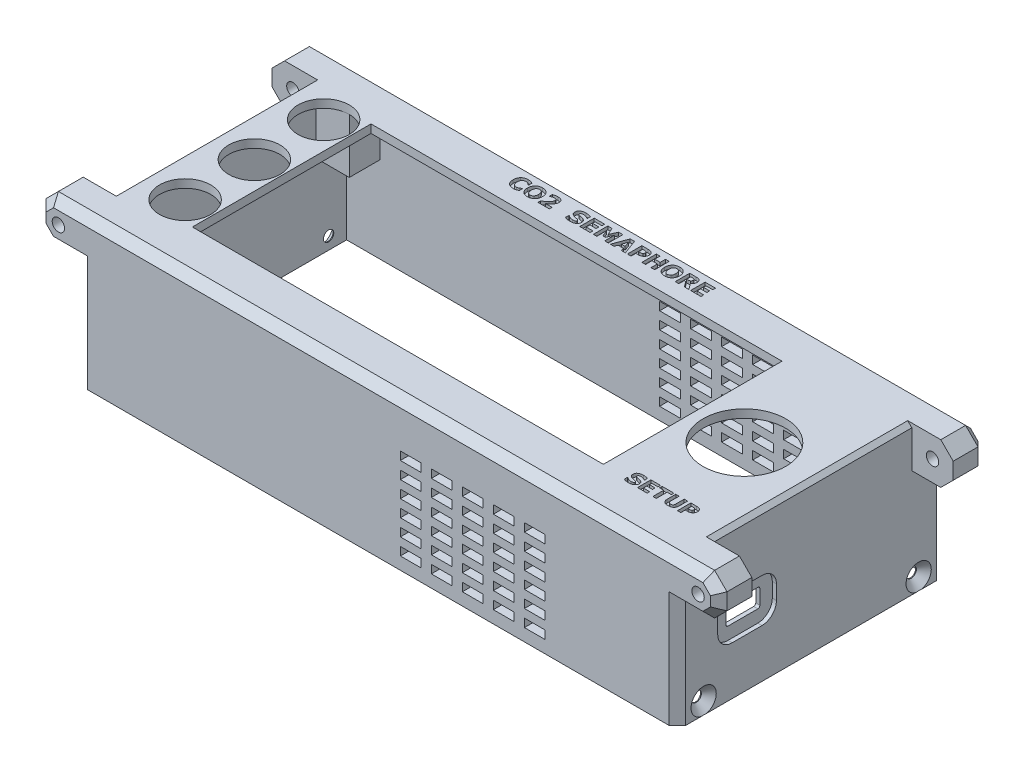
SolidWorks part; units mm, degrees
ref_plane "Спереди" through (0, 0, 0) normal (0, 0, 1) x (1, 0, 0)
ref_plane "Сверху" through (0, 0, 0) normal (0, 1, 0) x (1, 0, 0)
ref_plane "Справа" through (0, 0, 0) normal (1, 0, 0) x (0, 0, -1)
sketch "Эскиз1" plane through (0, 0, 0) normal (0, 1, 0) x (1, 0, 0)
  line L1 (-72.35, 32.35) -> (72.35, 32.35)
  line L2 (-72.35, 32.35) -> (-72.35, -32.35)
  line L3 (-72.35, -32.35) -> (72.35, -32.35)
  line L4 (72.35, 32.35) -> (72.35, -32.35)
  line L5 (-72.35, 32.35) -> (72.35, -32.35) construction
  line L6 (-72.35, -32.35) -> (72.35, 32.35) construction
  point P0 (0, 0)
  dimension "D1" = 144.7
  dimension "D2" = 64.7
extrude "Бобышка-Вытянуть1" add sketch "Эскиз1" along normal blind 36
sketch "Эскиз2" plane through (0, 0, 0) normal (0, -1, 0) x (1, 0, 0)
  line L1 (-70.35, 30.35) -> (70.35, 30.35)
  line L2 (-70.35, 30.35) -> (-70.35, -30.35)
  line L3 (-70.35, -30.35) -> (70.35, -30.35)
  line L4 (70.35, 30.35) -> (70.35, -30.35)
  line L5 (-70.35, 30.35) -> (70.35, -30.35) construction
  line L6 (-70.35, -30.35) -> (70.35, 30.35) construction
  point P0 (0, 0)
  dimension "D1" = 140.7
  dimension "D2" = 60.7
extrude "Вырез-Вытянуть1" cut sketch "Эскиз2" against normal offset from surface (34 mm away) 2 up to face at (0, 36, 0)
sketch "Эскиз3" plane through (0, 36, 0) normal (0, 1, 0) x (1, 0, 0)
  line L0 (42, 19.9) -> (-54, 19.9) construction
  line L1 (-55.7, 21.6) -> (43.7, 21.6)
  line L2 (-55.7, 21.6) -> (-55.7, -21.6)
  line L3 (-55.7, -21.6) -> (43.7, -21.6)
  line L4 (43.7, 21.6) -> (43.7, -21.6)
  line L5 (42, -19.9) -> (42, 19.9) construction
  line L6 (-54, -19.9) -> (42, -19.9) construction
  line L7 (-54, 19.9) -> (-54, -19.9) construction
  dimension "D1" = 1.7
  dimension "D2" = 1.7
  dimension "D3" = 1.7
  dimension "D4" = 1.7
extrude "Вырез-Вытянуть2" cut sketch "Эскиз3" against normal up to surface (2 mm away) up to face at (0, 34, 0)
sketch "Эскиз4" plane through (0, 36, 0) normal (0, 1, 0) x (1, 0, 0)
  circle A0 centre (-62.3, 16.75) radius 6.2
  circle A1 centre (-62.3, 0) radius 6.2
  circle A2 centre (-62.3, -16.75) radius 6.2
  dimension "D1" = 12.4
extrude "Вырез-Вытянуть3" cut sketch "Эскиз4" against normal up to surface (2 mm away) up to face at (-6, 34, 0)
sketch "Эскиз5" plane through (0, 36, 0) normal (0, 1, 0) x (1, 0, 0)
  circle A0 centre (56.2, 0) radius 10
  dimension "D1" = 20
extrude "Вырез-Вытянуть4" cut sketch "Эскиз5" against normal up to surface (2 mm away) up to face at (-62.3, 34, 6.2)
sketch "Эскиз6" plane through (72.35, 0, 0) normal (1, 0, 0) x (0, 0, -1)
  line L0 (-19.2, 16.9) -> (-19.2, 15.3) construction
  line L1 (-11.9, 14.7) -> (-19.1, 14.7)
  line L2 (-11.4, 15.2) -> (-11.4, 18.7)
  line L3 (-11.9, 19.2) -> (-19.1, 19.2)
  line L4 (-19.6, 15.2) -> (-19.6, 18.7)
  line L5 (-12, 15.1) -> (-19, 15.1) construction
  line L6 (-18.5, 18.8) -> (-12.5, 18.8) construction
  line L7 (-11.8, 16.9) -> (-11.8, 15.3) construction
  arc A0 (-11.4, 18.7) -> (-11.9, 19.2) centre (-11.9, 18.7) ccw
  arc A1 (-11.9, 14.7) -> (-11.4, 15.2) centre (-11.9, 15.2) ccw
  arc A2 (-19.1, 14.7) -> (-19.6, 15.2) centre (-19.1, 15.2) cw
  arc A3 (-19.1, 19.2) -> (-19.6, 18.7) centre (-19.1, 18.7) ccw
  dimension "D5" = 0.5
  dimension "D1" = 0.4
  dimension "D2" = 0.4
  dimension "D3" = 0.4
  dimension "D4" = 0.4
extrude "Вырез-Вытянуть5" cut sketch "Эскиз6" against normal up to surface (2 mm away) up to face at (70.35, 17, 0)
sketch "Эскиз7" plane through (72.35, 0, 0) normal (1, 0, 0) x (0, 0, -1)
  line L4 (-11.9, 19.2) -> (-19.1, 19.2) construction
  line L5 (-11.4, 15.2) -> (-11.4, 18.7) construction
  line L6 (-19.1, 14.7) -> (-11.9, 14.7) construction
  line L7 (-19.6, 18.7) -> (-19.6, 15.2) construction
  line L8 (-19.6, 18.7) -> (-19.6, 15.2) construction
  line L9 (-19.1, 14.7) -> (-11.9, 14.7) construction
  line L10 (-11.4, 15.2) -> (-11.4, 18.7) construction
  line L11 (-11.9, 19.2) -> (-19.1, 19.2) construction
  line L12 (-22.6, 18.7) -> (-22.6, 15.2)
  line L13 (-19.1, 11.7) -> (-11.9, 11.7)
  line L14 (-8.4, 15.2) -> (-8.4, 18.7)
  line L15 (-11.9, 22.2) -> (-19.1, 22.2)
  arc A0 (-11.4, 18.7) -> (-11.9, 19.2) centre (-11.9, 18.7) ccw construction
  arc A3 (-11.9, 14.7) -> (-11.4, 15.2) centre (-11.9, 15.2) ccw construction
  arc A4 (-19.6, 15.2) -> (-19.1, 14.7) centre (-19.1, 15.2) ccw construction
  arc A5 (-19.1, 19.2) -> (-19.6, 18.7) centre (-19.1, 18.7) ccw construction
  arc A6 (-19.1, 19.2) -> (-19.6, 18.7) centre (-19.1, 18.7) ccw construction
  arc A7 (-19.6, 15.2) -> (-19.1, 14.7) centre (-19.1, 15.2) ccw construction
  arc A8 (-11.9, 14.7) -> (-11.4, 15.2) centre (-11.9, 15.2) ccw construction
  arc A9 (-11.4, 18.7) -> (-11.9, 19.2) centre (-11.9, 18.7) ccw construction
  arc A10 (-22.6, 15.2) -> (-19.1, 11.7) centre (-19.1, 15.2) ccw
  arc A11 (-11.9, 11.7) -> (-8.4, 15.2) centre (-11.9, 15.2) ccw
  arc A12 (-8.4, 18.7) -> (-11.9, 22.2) centre (-11.9, 18.7) ccw
  arc A13 (-19.1, 22.2) -> (-22.6, 18.7) centre (-19.1, 18.7) ccw
  dimension "D1" = 3
extrude "Вырез-Вытянуть6" cut sketch "Эскиз7" against normal blind 1
sketch "Эскиз8" plane through (0, 34, 0) normal (0, -1, 0) x (1, 0, 0)
  circle A0 centre (-66, 26) radius 1.5
  circle A1 centre (-66, -26) radius 1.5
  circle A2 centre (66, 26) radius 1.5
  circle A3 centre (66, -26) radius 1.5
sketch "Эскиз9" plane through (0, 34, 0) normal (0, -1, 0) x (1, 0, 0)
  line L1 (-70.35, 30.35) -> (-62.3, 30.35)
  line L2 (-70.35, 30.35) -> (-70.35, 22.95)
  line L3 (-70.35, 22.95) -> (-62.3, 22.95)
  line L4 (-62.3, 30.35) -> (-62.3, 22.95)
  line L5 (-70.35, -30.35) -> (-62.3, -30.35)
  line L6 (-70.35, -30.35) -> (-70.35, -22.95)
  line L7 (-70.35, -22.95) -> (-62.3, -22.95)
  line L8 (-62.3, -30.35) -> (-62.3, -22.95)
  line L9 (70.35, 30.35) -> (62.3, 30.35)
  line L10 (70.35, 30.35) -> (70.35, 22.95)
  line L11 (70.35, 22.95) -> (62.3, 22.95)
  line L12 (62.3, 30.35) -> (62.3, 22.95)
  line L13 (70.35, -30.35) -> (62.3, -30.35)
  line L14 (70.35, -30.35) -> (70.35, -22.95)
  line L15 (70.35, -22.95) -> (62.3, -22.95)
  line L16 (62.3, -30.35) -> (62.3, -22.95)
  circle A0 centre (-62.3, 16.75) radius 6.2 construction
  circle A1 centre (-62.3, -16.75) radius 6.2 construction
  dimension "D1" = 8.05
  dimension "D2" = 8.05
extrude "Бобышка-Вытянуть2" add sketch "Эскиз9" along normal blind 13.2
sketch "Эскиз10" plane through (0, 20.8, 0) normal (0, -1, 0) x (1, 0, 0)
  circle A0 centre (66, 26) radius 1.5 construction
  circle A1 centre (66, -26) radius 1.5 construction
  circle A2 centre (-66, -26) radius 1.5 construction
  circle A3 centre (-66, 26) radius 1.5 construction
  circle A4 centre (66, 26) radius 1.5
  circle A5 centre (66, -26) radius 1.5
  circle A6 centre (-66, -26) radius 1.5
  circle A7 centre (-66, 26) radius 1.5
  circle A8 centre (-66, 26) radius 1
  circle A9 centre (-66, -26) radius 1
  circle A10 centre (66, -26) radius 1
  circle A11 centre (66, 26) radius 1
  dimension "D1" = 0.5
extrude "Вырез-Вытянуть7" cut sketch "Эскиз10" against normal up to surface (13.2 mm away) contours A8 | A9 | A10 | A11 region at (-66, 20.8, 26) region at (-66, 20.8, -26) region at (66, 20.8, -26) region at (66, 20.8, 26) up to face at (56.2, 34, 10)
sketch "Эскиз11" plane through (72.35, 0, 0) normal (1, 0, 0) x (0, 0, -1)
  line L0 (-32.35, 36) -> (32.35, 36) construction
  line L1 (-32.35, 36) -> (-24.35, 36)
  line L2 (-32.35, 36) -> (-32.35, 26)
  line L3 (-32.35, 26) -> (-24.35, 26)
  line L4 (-24.35, 36) -> (-24.35, 26)
  line L5 (32.35, 36) -> (24.35, 36)
  line L6 (32.35, 36) -> (32.35, 26)
  line L7 (32.35, 26) -> (24.35, 26)
  line L8 (24.35, 36) -> (24.35, 26)
  line L9 (32.35, 36) -> (32.35, 0) construction
  dimension "D1" = 8
  dimension "D2" = 8
  dimension "D3" = 10
extrude "Бобышка-Вытянуть3" add sketch "Эскиз11" along normal blind 10
sketch "Эскиз12" plane through (0, 0, 32.35) normal (0, 0, 1) x (1, 0, 0)
  line L0 (79.35, 26) -> (79.35, 36) construction
  line L1 (82.35, 26) -> (72.35, 26) construction
  line L2 (-72.35, 36) -> (82.35, 36) construction
  line L3 (82.35, 29) -> (72.35, 29) construction
  line L4 (82.35, 36) -> (82.35, 26) construction
  line L5 (82.35, 33) -> (72.35, 33) construction
  line L6 (79.35, 36) -> (82.35, 33)
  line L7 (82.35, 33) -> (82.35, 36)
  line L8 (82.35, 36) -> (79.35, 36)
  line L9 (79.35, 26) -> (82.35, 29)
  line L10 (82.35, 29) -> (82.35, 26)
  line L11 (82.35, 26) -> (79.35, 26)
  dimension "D1" = 3
  dimension "D2" = 3
  dimension "D3" = 3
extrude "Вырез-Вытянуть8" cut sketch "Эскиз12" against normal up to surface (64.7 mm away) up to face at (27.45, 20.6667, -32.35)
sketch "Эскиз13" plane through (-72.35, 0, 0) normal (-1, 0, 0) x (0, 0, 1)
  line L1 (-32.35, 36) -> (-24.35, 36)
  line L2 (-32.35, 36) -> (-32.35, 26)
  line L3 (-32.35, 26) -> (-24.35, 26)
  line L4 (-24.35, 36) -> (-24.35, 26)
  line L5 (32.35, 36) -> (24.35, 36)
  line L6 (32.35, 36) -> (32.35, 26)
  line L7 (32.35, 26) -> (24.35, 26)
  line L8 (24.35, 36) -> (24.35, 26)
  dimension "D1" = 8
  dimension "D2" = 10
  dimension "D3" = 8
extrude "Бобышка-Вытянуть4" add sketch "Эскиз13" along normal blind 10
sketch "Эскиз14" plane through (0, 0, 32.35) normal (0, 0, 1) x (1, 0, 0)
  line L0 (-79.35, 36) -> (-79.35, 26) construction
  line L1 (-82.35, 36) -> (79.35, 36) construction
  line L2 (-82.35, 26) -> (-72.35, 26) construction
  line L3 (-82.35, 33) -> (-72.35, 33) construction
  line L4 (-82.35, 26) -> (-82.35, 36) construction
  line L5 (-82.35, 29) -> (-72.35, 29) construction
  line L6 (-79.35, 26) -> (-82.35, 29)
  line L7 (-82.35, 29) -> (-82.35, 26)
  line L8 (-82.35, 26) -> (-79.35, 26)
  line L9 (-79.35, 36) -> (-82.35, 33)
  line L10 (-82.35, 33) -> (-82.35, 36)
  line L11 (-82.35, 36) -> (-79.35, 36)
  dimension "D1" = 3
  dimension "D2" = 3
  dimension "D3" = 3
extrude "Вырез-Вытянуть9" cut sketch "Эскиз14" against normal up to surface (64.7 mm away) up to face at (15.87, 23.8, -32.35)
sketch "Эскиз16" plane through (0, 0, 32.35) normal (0, 0, 1) x (1, 0, 0)
  line L0 (-82.35, 31) -> (82.35, 31) construction
  line L1 (-82.35, 29) -> (-82.35, 33) construction
  line L2 (82.35, 33) -> (82.35, 29) construction
  line L3 (-77.35, 36) -> (-77.35, 26) construction
  line L4 (-79.35, 36) -> (79.35, 36) construction
  line L5 (-79.35, 26) -> (-72.35, 26) construction
  line L6 (0, 36) -> (0, 0) construction
  circle A0 centre (-77.35, 31) radius 1.5
  circle A1 centre (77.35, 31) radius 1.5
  dimension "D2" = 3
  dimension "D1" = 5
extrude "Вырез-Вытянуть10" cut sketch "Эскиз16" against normal offset from surface (59.7 mm away) 5 up to face at (0, 25, -32.35)
sketch "Эскиз17" plane through (0, 0, -32.35) normal (0, 0, -1) x (-1, 0, 0)
  line L0 (-40.35, 36) -> (-40.35, 0) construction
  line L1 (-79.35, 36) -> (79.35, 36) construction
  line L2 (-72.35, 0) -> (72.35, 0) construction
  line L3 (-5.35, 36) -> (-5.35, 0) construction
  line L4 (-72.35, 26) -> (-72.35, 0) construction
  line L5 (-40.35, 25) -> (-5.35, 25) construction
  line L6 (-27.85, 25) -> (-27.85, 23)
  line L7 (-40.35, 25) -> (-35.35, 25)
  line L8 (-40.35, 25) -> (-40.35, 23)
  line L9 (-40.35, 23) -> (-35.35, 23)
  line L10 (-35.35, 25) -> (-35.35, 23)
  line L11 (-32.85, 25) -> (-27.85, 25)
  line L12 (-32.85, 23) -> (-27.85, 23)
  line L13 (-32.85, 25) -> (-32.85, 23)
  line L14 (-20.35, 25) -> (-20.35, 23)
  line L15 (-25.35, 25) -> (-20.35, 25)
  line L16 (-25.35, 23) -> (-20.35, 23)
  line L17 (-25.35, 25) -> (-25.35, 23)
  line L18 (-12.85, 25) -> (-12.85, 23)
  line L19 (-17.85, 25) -> (-12.85, 25)
  line L20 (-17.85, 23) -> (-12.85, 23)
  line L21 (-17.85, 25) -> (-17.85, 23)
  line L22 (-5.35, 25) -> (-5.35, 23)
  line L23 (-10.35, 25) -> (-5.35, 25)
  line L24 (-10.35, 23) -> (-5.35, 23)
  line L25 (-10.35, 25) -> (-10.35, 23)
  line L26 (-27.85, 21) -> (-27.85, 19)
  line L27 (-32.85, 21) -> (-27.85, 21)
  line L28 (-32.85, 19) -> (-27.85, 19)
  line L29 (-32.85, 21) -> (-32.85, 19)
  line L30 (-20.35, 21) -> (-20.35, 19)
  line L31 (-25.35, 21) -> (-20.35, 21)
  line L32 (-25.35, 19) -> (-20.35, 19)
  line L33 (-25.35, 21) -> (-25.35, 19)
  line L34 (-12.85, 21) -> (-12.85, 19)
  line L35 (-17.85, 21) -> (-12.85, 21)
  line L36 (-17.85, 19) -> (-12.85, 19)
  line L37 (-17.85, 21) -> (-17.85, 19)
  line L38 (-5.35, 21) -> (-5.35, 19)
  line L39 (-10.35, 21) -> (-5.35, 21)
  line L40 (-10.35, 19) -> (-5.35, 19)
  line L41 (-10.35, 21) -> (-10.35, 19)
  line L42 (-27.85, 17) -> (-27.85, 15)
  line L43 (-32.85, 17) -> (-27.85, 17)
  line L44 (-32.85, 15) -> (-27.85, 15)
  line L45 (-32.85, 17) -> (-32.85, 15)
  line L46 (-20.35, 17) -> (-20.35, 15)
  line L47 (-25.35, 17) -> (-20.35, 17)
  line L48 (-25.35, 15) -> (-20.35, 15)
  line L49 (-25.35, 17) -> (-25.35, 15)
  line L50 (-12.85, 17) -> (-12.85, 15)
  line L51 (-17.85, 17) -> (-12.85, 17)
  line L52 (-17.85, 15) -> (-12.85, 15)
  line L53 (-17.85, 17) -> (-17.85, 15)
  line L54 (-5.35, 17) -> (-5.35, 15)
  line L55 (-10.35, 17) -> (-5.35, 17)
  line L56 (-10.35, 15) -> (-5.35, 15)
  line L57 (-10.35, 17) -> (-10.35, 15)
  line L58 (-27.85, 13) -> (-27.85, 11)
  line L59 (-32.85, 13) -> (-27.85, 13)
  line L60 (-32.85, 11) -> (-27.85, 11)
  line L61 (-32.85, 13) -> (-32.85, 11)
  line L62 (-20.35, 13) -> (-20.35, 11)
  line L63 (-25.35, 13) -> (-20.35, 13)
  line L64 (-25.35, 11) -> (-20.35, 11)
  line L65 (-25.35, 13) -> (-25.35, 11)
  line L66 (-12.85, 13) -> (-12.85, 11)
  line L67 (-17.85, 13) -> (-12.85, 13)
  line L68 (-17.85, 11) -> (-12.85, 11)
  line L69 (-17.85, 13) -> (-17.85, 11)
  line L70 (-5.35, 13) -> (-5.35, 11)
  line L71 (-10.35, 13) -> (-5.35, 13)
  line L72 (-10.35, 11) -> (-5.35, 11)
  line L73 (-10.35, 13) -> (-10.35, 11)
  line L74 (-27.85, 9) -> (-27.85, 7)
  line L75 (-32.85, 9) -> (-27.85, 9)
  line L76 (-32.85, 7) -> (-27.85, 7)
  line L77 (-32.85, 9) -> (-32.85, 7)
  line L78 (-20.35, 9) -> (-20.35, 7)
  line L79 (-25.35, 9) -> (-20.35, 9)
  line L80 (-25.35, 7) -> (-20.35, 7)
  line L81 (-25.35, 9) -> (-25.35, 7)
  line L82 (-12.85, 9) -> (-12.85, 7)
  line L83 (-17.85, 9) -> (-12.85, 9)
  line L84 (-17.85, 7) -> (-12.85, 7)
  line L85 (-17.85, 9) -> (-17.85, 7)
  line L86 (-5.35, 9) -> (-5.35, 7)
  line L87 (-10.35, 9) -> (-5.35, 9)
  line L88 (-10.35, 7) -> (-5.35, 7)
  line L89 (-10.35, 9) -> (-10.35, 7)
  line L90 (-27.85, 5) -> (-27.85, 3)
  line L91 (-32.85, 5) -> (-27.85, 5)
  line L92 (-32.85, 3) -> (-27.85, 3)
  line L93 (-32.85, 5) -> (-32.85, 3)
  line L94 (-20.35, 5) -> (-20.35, 3)
  line L95 (-25.35, 5) -> (-20.35, 5)
  line L96 (-25.35, 3) -> (-20.35, 3)
  line L97 (-25.35, 5) -> (-25.35, 3)
  line L98 (-12.85, 5) -> (-12.85, 3)
  line L99 (-17.85, 5) -> (-12.85, 5)
  line L100 (-17.85, 3) -> (-12.85, 3)
  line L101 (-17.85, 5) -> (-17.85, 3)
  line L102 (-5.35, 5) -> (-5.35, 3)
  line L103 (-10.35, 5) -> (-5.35, 5)
  line L104 (-10.35, 3) -> (-5.35, 3)
  line L105 (-10.35, 5) -> (-10.35, 3)
  line L106 (-35.35, 21) -> (-35.35, 19)
  line L107 (-40.35, 21) -> (-35.35, 21)
  line L108 (-40.35, 19) -> (-35.35, 19)
  line L109 (-40.35, 21) -> (-40.35, 19)
  line L110 (-35.35, 17) -> (-35.35, 15)
  line L111 (-40.35, 17) -> (-35.35, 17)
  line L112 (-40.35, 15) -> (-35.35, 15)
  line L113 (-40.35, 17) -> (-40.35, 15)
  line L114 (-35.35, 13) -> (-35.35, 11)
  line L115 (-40.35, 13) -> (-35.35, 13)
  line L116 (-40.35, 11) -> (-35.35, 11)
  line L117 (-40.35, 13) -> (-40.35, 11)
  line L118 (-35.35, 9) -> (-35.35, 7)
  line L119 (-40.35, 9) -> (-35.35, 9)
  line L120 (-40.35, 7) -> (-35.35, 7)
  line L121 (-40.35, 9) -> (-40.35, 7)
  line L122 (-35.35, 5) -> (-35.35, 3)
  line L123 (-40.35, 5) -> (-35.35, 5)
  line L124 (-40.35, 3) -> (-35.35, 3)
  line L125 (-40.35, 5) -> (-40.35, 3)
  dimension "D1" = 32
  dimension "D2" = 35
  dimension "D3" = 25
  dimension "D4" = 5
  dimension "D5" = 2
  dimension "D6" = 5
  dimension "D7" = 6
extrude "Вырез-Вытянуть11" cut sketch "Эскиз17" against normal up to surface (64.7 mm away) up to face at (75.85, 31, 32.35)
chamfer "Фаска1" distance 2 angle 45 4 edges at (72.35, 13, 32.35) (72.35, 13, -32.35) (-72.35, 13, -32.35) (-72.35, 13, 32.35)
chamfer "Фаска2" distance 2 angle 45 9 edges at (-74.85, 26, -32.35) (-80.85, 27.5, -32.35) (-82.35, 31, -32.35) (-80.85, 34.5, -32.35) (74.85, 26, -32.35) (80.85, 27.5, -32.35) (82.35, 31, -32.35) (80.85, 34.5, -32.35) (0, 36, -32.35)
chamfer "Фаска3" distance 2 angle 45 9 edges at (74.85, 26, 32.35) (80.85, 27.5, 32.35) (82.35, 31, 32.35) (80.85, 34.5, 32.35) (-74.85, 26, 32.35) (-80.85, 27.5, 32.35) (-82.35, 31, 32.35) (-80.85, 34.5, 32.35) (0, 36, 32.35)
sketch "Эскиз18" plane through (0, 36, 0) normal (0, 1, 0) x (1, 0, 0)
  line L0 (46.1, -22.35) -> (72.35, -22.35) construction
  line L1 (46.1, -16.8) -> (46.1, -22.3) construction
  line L2 (72.35, -24.35) -> (72.35, 24.35) construction
  line L3 (78.5216, -32.35) -> (-78.5216, -32.35) construction
  text T0 "  SETUP" font "Verdana" height in points 12
  dimension "D1" = 10
extrude "Вырез-Вытянуть12" cut sketch "Эскиз18" against normal blind 0.8
chamfer "Фаска4" distance 1 angle 45 2 edges at (72.35, 36, 0) (-72.35, 36, 0)
sketch "Эскиз19" plane through (-70.35, 0, 0) normal (1, 0, 0) x (0, 0, -1)
  circle A0 centre (-26, 3) radius 1.25
  circle A1 centre (26, 3) radius 1.25
extrude "Вырез-Вытянуть13" cut sketch "Эскиз19" against normal up to surface and the other way up to surface up to face at (-72.35, 21.75, 0) other way up to face at (72.35, 16.95, 15.5)
chamfer "Фаска5" distance 1.8 angle 45 4 edges at (72.35, 3, -24.75) (72.35, 3, 27.25) (-72.35, 3, 24.75) (-72.35, 3, -27.25)
sketch "Эскиз20" plane through (0, 36, 0) normal (0, 1, 0) x (1, 0, 0)
  line L0 (71.35, 25.35) -> (-79.35, 25.35) construction
  line L1 (71.35, -24.35) -> (71.35, 24.35) construction
  line L4 (-78.5216, 32.35) -> (78.5216, 32.35) construction
  line L5 (-79.35, 30.35) -> (-79.35, 24.35) construction
  text T0 " CO2  SEMAPHORE" font "Verdana" height 3.5
  point P4 (-79.35, 26.35)
  point P7 (46.1, 26.35)
  dimension "D1" = 7
extrude "Вырез-Вытянуть14" cut sketch "Эскиз20" against normal blind 0.8
